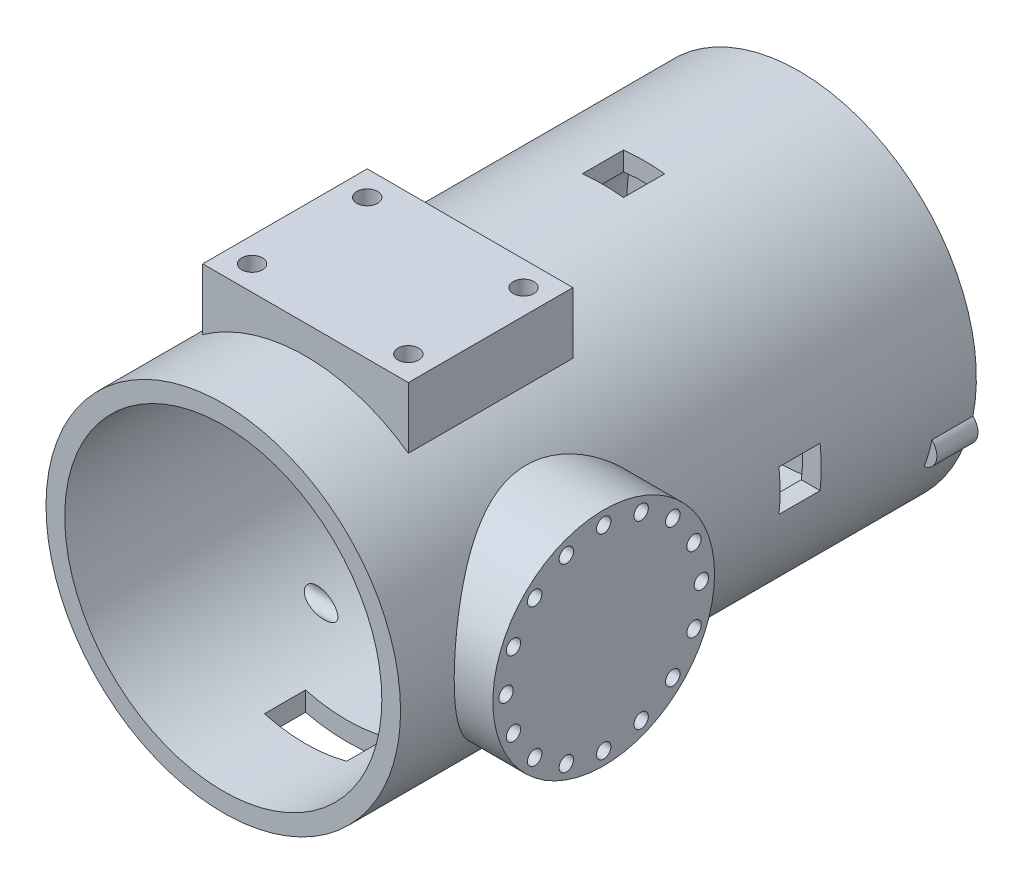
SolidWorks part; units mm, degrees
other "Markup1"
sketch "Sketch14" plane through (-43.1, 43.1, 140) normal (-0.1765, 0.0048, 0.9843) x (0.9842, -0.0149, 0.1765)
other "Markup2"
sketch "Sketch23" plane through (45.1, -43.1, 140) normal (0.9491, -0.0629, 0.3087) x (0.311, 0.031, -0.9499)
ref_plane "Front Plane" through (0, 0, 0) normal (0, 0, 1) x (1, 0, 0)
ref_plane "Top Plane" through (0, 0, 0) normal (0, 1, 0) x (1, 0, 0)
ref_plane "Right Plane" through (0, 0, 0) normal (1, 0, 0) x (0, 0, -1)
sketch "Sketch1" plane through (0, 0, 0) normal (0, 0, 1) x (1, 0, 0)
  circle A1 centre (0, 0) radius 43.1
  dimension "D1" = 86.2
extrude "Main Body" add sketch "Sketch1" along normal blind 140
ref_plane "Plane1" through (0, 43.1, 0) normal (0, 1, 0) x (1, 0, 0)
sketch "Sketch34" [suppressed] plane through (0, 43.1, 0) normal (0, 1, 0) x (1, 0, 0)
  line L6 (-5, -13) -> (5, -13)
  line L8 (-5, -13) -> (-5, -3)
  line L9 (-5, -3) -> (5, -3)
  line L10 (5, -13) -> (5, -3)
  line L11 (-5, -13) -> (5, -3) construction
  line L12 (-5, -3) -> (5, -13) construction
  point P0 (0, -8)
  dimension "D1" = 8
  dimension "D2" = 10
  dimension "D3" = 10
sketch "Sketch6" plane through (0, 43.1, 0) normal (0, 1, 0) x (1, 0, 0)
  line L2 (-5, -47.7) -> (5, -47.7)
  line L3 (-5, -47.7) -> (-5, -37.7)
  line L4 (-5, -37.7) -> (5, -37.7)
  line L5 (5, -47.7) -> (5, -37.7)
  line L6 (-5, -47.7) -> (5, -37.7) construction
  line L7 (-5, -37.7) -> (5, -47.7) construction
  point P2 (0, -42.7)
  dimension "D2" = 10
  dimension "D1" = 42.7
  dimension "D3" = 10
extrude "Cut-Extrude3" cut sketch "Sketch6" against normal through all
pattern_circular "Rotated Plug Pattern" count 2 every 90 about axis through (0, 0, 140) along (0, 0, 1) of "Cut-Extrude3"
ref_plane "Plane2" through (52.5, 0, 0) normal (1, 0, 0) x (0, 0, -1)
sketch "Sketch8" plane through (52.5, 0, 0) normal (1, 0, 0) x (0, 0, -1)
  circle A0 centre (-100, 0) radius 26.95
  dimension "D1" = 53.9
  dimension "D2" = 100
extrude "Boss-Extrude2" add sketch "Sketch8" against normal blind 20
mirror "Mirror1" [suppressed] about plane through (0, 0, 0) normal (1, 0, 0)
ref_plane "Plane3" through (0, 50, 0) normal (0, 1, 0) x (1, 0, 0)
sketch "Sketch33" plane through (0, 50, 0) normal (0, 1, 0) x (1, 0, 0)
  line L1 (-25, -120) -> (25, -120)
  line L2 (-25, -120) -> (-25, -80)
  line L3 (-25, -80) -> (25, -80)
  line L4 (25, -120) -> (25, -80)
  line L5 (-25, -120) -> (25, -80) construction
  line L6 (-25, -80) -> (25, -120) construction
  point P0 (0, -100)
  dimension "D1" = 100
  dimension "D2" = 40
  dimension "D3" = 50
extrude "Boss-Extrude11" add sketch "Sketch33" against normal blind 22
sketch "Sketch35" plane through (0, 50, 0) normal (0, 1, 0) x (1, 0, 0)
  line L0 (-25, -120) -> (-25, -80) construction
  line L1 (25, -120) -> (25, -80) construction
  line L2 (25, -80) -> (-25, -80) construction
  line L3 (-25, -120) -> (25, -120) construction
  circle A0 centre (-19, -86) radius 2.525
  circle A1 centre (19, -86) radius 2.525
  circle A2 centre (-19, -114) radius 2.525
  circle A3 centre (19, -114) radius 2.525
  dimension "D1" = 5.05
  dimension "D2" = 6
  dimension "D3" = 6
  dimension "D4" = 6
  dimension "D5" = 6
extrude "Cut-Extrude14" cut sketch "Sketch35" against normal blind 4
sketch "Sketch5" plane through (0, 0, 140) normal (0, 0, 1) x (1, 0, 0)
  circle A0 centre (0, 0) radius 32
  dimension "D1" = 64
extrude "Hole 1" cut sketch "Sketch5" against normal through all
sketch "Sketch10" plane through (0, 0, 0) normal (0, 1, 0) x (1, 0, 0)
  line L0 (43.1, 0) -> (-43.1, 0) construction
  line L1 (-10, -120) -> (10, -120)
  line L2 (-10, -120) -> (-10, -110)
  line L3 (-10, -110) -> (10, -110)
  line L4 (10, -120) -> (10, -110)
  line L5 (-10, -120) -> (10, -110) construction
  line L6 (-10, -110) -> (10, -120) construction
  point P0 (0, -115)
  point P7 (-10, -115)
  dimension "D1" = 110
  dimension "D2" = 10
  dimension "D3" = 20
extrude "Motor Wire Hole" cut sketch "Sketch10" against normal through all
sketch "Sketch27" plane through (0, 0, 0) normal (1, 0, 0) x (0, 0, -1)
  line L1 (-100, -36.5) -> (-60, -36.5)
  line L2 (-100, -36.5) -> (-100, -27.5)
  line L3 (-100, -27.5) -> (-60, -27.5)
  line L4 (-60, -36.5) -> (-60, -27.5)
  dimension "D1" = 60
  dimension "D2" = 27.5
  dimension "D3" = 40
  dimension "D4" = 9
extrude "Boss-Extrude9" add sketch "Sketch27" along normal blind 33 and the other way blind 33
sketch "Sketch11" plane through (0, 0, 0) normal (1, 0, 0) x (0, 0, -1)
  circle A0 centre (-65, -32) radius 2.25
  circle A1 centre (-95, -32) radius 2.25
  dimension "D3" = 4.5
  dimension "D1" = 65
  dimension "D2" = 32
  dimension "D4" = 30
extrude "Cut-Extrude6" cut sketch "Sketch11" against normal through all both and the other way through all
sketch "Sketch28" plane through (-33, 0, 0) normal (-1, 0, 0) x (0, 0, 1)
  line L0 (62.8927, -28.35) -> (67.1073, -28.35)
  line L1 (67.1073, -28.35) -> (69.2147, -32)
  line L2 (69.2147, -32) -> (67.1073, -35.65)
  line L3 (67.1073, -35.65) -> (62.8927, -35.65)
  line L4 (62.8927, -35.65) -> (60.7853, -32)
  line L6 (60.7853, -32) -> (62.8927, -28.35)
  line L7 (92.8927, -28.35) -> (97.1073, -28.35)
  line L8 (97.1073, -28.35) -> (99.2147, -32)
  line L9 (99.2147, -32) -> (97.1073, -35.65)
  line L10 (97.1073, -35.65) -> (92.8927, -35.65)
  line L11 (92.8927, -35.65) -> (90.7853, -32)
  line L12 (90.7853, -32) -> (92.8927, -28.35)
  circle A0 centre (65, -32) radius 3.65 construction
  circle A1 centre (65, -32) radius 2.25 construction
  circle A2 centre (95, -32) radius 3.65 construction
  circle A3 centre (95, -32) radius 2.25 construction
  dimension "D2" = 7.3
extrude "Cut-Extrude7" cut sketch "Sketch28" against normal blind 3
sketch "Sketch29" plane through (33, 0, 0) normal (1, 0, 0) x (0, 0, -1)
  circle A0 centre (-95, -32) radius 3.6
  circle A1 centre (-65, -32) radius 3.6
  dimension "D1" = 7.2
extrude "Cut-Extrude8" cut sketch "Sketch29" against normal blind 4
sketch "Sketch2" plane through (0, 0, 140) normal (0, 0, 1) x (1, 0, 0)
  circle A0 centre (0, 0) radius 38.55
  dimension "D1" = 77.1
extrude "Cut-Extrude5" cut sketch "Sketch2" against normal blind 135
sketch "Sketch9" plane through (0, 0, 5) normal (0, 0, 1) x (1, 0, 0)
  circle A0 centre (0, 0) radius 38.55
  circle A1 centre (0, 0) radius 36.89
  circle A2 centre (0, 0) radius 38.55 construction
  dimension "D2" = 1.66
extrude "Boss-Extrude3" add sketch "Sketch9" along normal blind 10
extrude "Cut-Extrude13" [suppressed] cut sketch "Sketch34" against normal blind 15
sketch "Sketch30" plane through (52.5, 0, 0) normal (1, 0, 0) x (0, 0, -1)
  line L0 (-100, 23.75) -> (-100, 0) construction
  circle A0 centre (-100, 0) radius 23.75 construction
  circle A1 centre (-100, 23.75) radius 1.75
  circle A2 centre (-90.9113, 21.9421) radius 1.75
  circle A3 centre (-83.2062, 16.7938) radius 1.75
  circle A4 centre (-78.0579, 9.0887) radius 1.75
  circle A5 centre (-76.25, 0) radius 1.75
  circle A6 centre (-78.0579, -9.0887) radius 1.75
  circle A7 centre (-83.2062, -16.7938) radius 1.75
  circle A8 centre (-90.9113, -21.9421) radius 1.75
  circle A9 centre (-100, -23.75) radius 1.75
  circle A10 centre (-109.0887, -21.9421) radius 1.75
  circle A11 centre (-116.7938, -16.7938) radius 1.75
  circle A12 centre (-121.9421, -9.0887) radius 1.75
  circle A13 centre (-123.75, 0) radius 1.75
  circle A14 centre (-121.9421, 9.0887) radius 1.75
  circle A15 centre (-116.7938, 16.7938) radius 1.75
  circle A16 centre (-109.0887, 21.9421) radius 1.75
  point P38 (-100, 0)
  dimension "D1" = 47.5
  dimension "D2" = 3.5
  dimension "D3" = 16
extrude "Cut-Extrude9" cut sketch "Sketch30" against normal up to surface (22.1349 mm away) up to face at (38.55, 0, 15)
sketch "Sketch31" plane through (52.5, 0, 0) normal (1, 0, 0) x (0, 0, -1)
  line L0 (0, -43.1) -> (0, 43.1) construction
  line L1 (0, -15) -> (-10, -15)
  line L2 (0, -15) -> (0, -7.5)
  line L3 (0, -7.5) -> (-10, -7.5)
  line L4 (-10, -15) -> (-10, -7.5)
  dimension "D1" = 15
  dimension "D2" = 7.5
  dimension "D3" = 10
extrude "Boss-Extrude10" add sketch "Sketch31" against normal up to body from offset 9 offset against normal yes
sketch "Sketch32" plane through (0, 0, 0) normal (0, 0, -1) x (-1, 0, 0)
  line L0 (-43.5, -11.25) -> (-29.9573, -11.25) construction
  line L1 (-43.5, -15) -> (-43.5, -7.5) construction
  line L3 (-42.4424, -7.5) -> (-43.5, -7.5) construction
  line L5 (-43.5, -15) -> (-43.5, -7.5)
  line L6 (-43.5, -7.5) -> (-42.4424, -7.5)
  circle A0 centre (0, 0) radius 32 construction
  arc A2 (-40.4056, -15) -> (-42.4424, -7.5) centre (0, 0) ccw construction
  arc A3 (-40.4056, -15) -> (-42.2658, -8.4385) centre (-39.6806, -11.25) cw
  arc A4 (-42.2658, -8.4385) -> (-42.4424, -7.5) centre (0, 0) cw
  line M3 (-42.4424, -7.5) -> (-43.5, -7.5)
  line M4 (-43.5, -7.5) -> (-43.5, -15)
  line M5 (-43.5, -15) -> (-40.4056, -15)
extrude "Cut-Extrude10" cut sketch "Sketch32" against normal up to surface (10 mm away) contours M4 M3 | L5 M5 region at (43.0347, -8.5479, 0) region at (42.7123, -14.1508, 0) up to face at (42.5043, -11.2615, 10)
ref_plane "Plane4" through (-43.1, 0, 0) normal (-1, 0, 0) x (0, 0, 1)
sketch "Sketch36" plane through (-43.1, 0, 0) normal (-1, 0, 0) x (0, 0, 1)
  line L0 (140, -43.1) -> (140, 43.1) construction
  line L1 (47.41, 43.1) -> (-47.41, 43.1) construction
  circle A0 centre (110, 8.1) radius 19.05
  dimension "D1" = 38.1
  dimension "D2" = 30
  dimension "D3" = 35
extrude "Cut-Extrude15" [suppressed] cut sketch "Sketch36" against normal up to next
